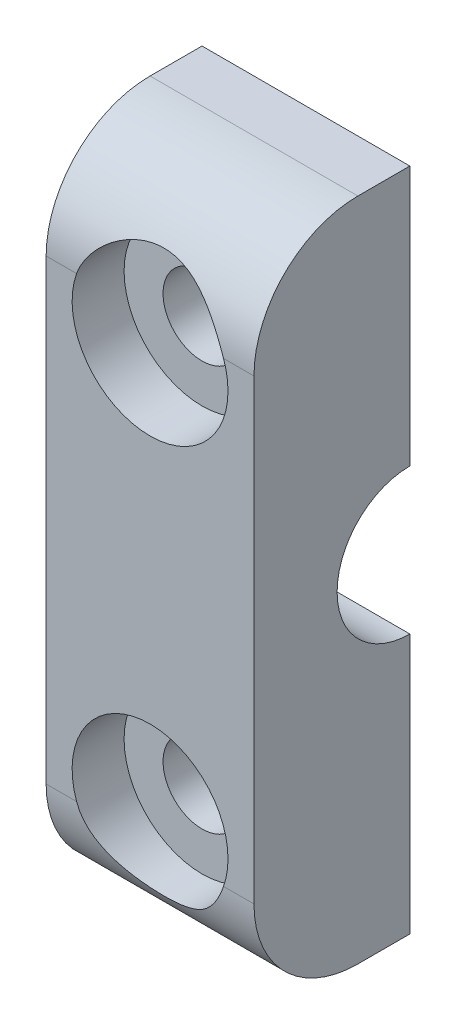
SolidWorks part; units mm, degrees
ref_plane "Alzado" through (0, 0, 0) normal (0, 0, 1) x (1, 0, 0)
ref_plane "Planta" through (0, 0, 0) normal (0, 1, 0) x (1, 0, 0)
ref_plane "Vista lateral" through (0, 0, 0) normal (1, 0, 0) x (0, 0, -1)
sketch "Croquis1" plane through (0, 0, 0) normal (0, 0, 1) x (1, 0, 0)
  line L0 (-132.4409, 66.7992) -> (-124.4409, 66.7992)
  line L1 (-132.4409, 66.7992) -> (-132.4409, 41.1992)
  line L2 (-132.4409, 41.1992) -> (-124.4409, 41.1992)
  line L3 (-124.4409, 66.7992) -> (-124.4409, 41.1992)
  circle A0 centre (-128.4409, 61.7992) radius 1.5
  circle A1 centre (-128.4409, 46.1992) radius 1.5
  dimension "D1" = 25.6
extrude "Saliente-Extruir1" add sketch "Croquis1" along normal blind 6
fillet "Redondeo1" radius 4 2 edges at (-128.4409, 66.7992, 6) (-128.4409, 41.1992, 6)
sketch "Croquis2" plane through (0, 0, 6) normal (0, 0, 1) x (1, 0, 0)
  circle A0 centre (-128.4409, 46.1992) radius 3
  circle A1 centre (-128.4409, 61.7992) radius 3
extrude "Cortar-Extruir1" cut sketch "Croquis2" against normal blind 2
sketch "Croquis3" plane through (-124.4409, 0, 0) normal (1, 0, 0) x (0, 0, -1)
  line L0 (0, 41.1992) -> (0, 66.7992) construction
  circle A0 centre (0, 53.9992) radius 2.8
extrude "Cortar-Extruir2" cut sketch "Croquis3" against normal up to vertex (8 mm away) up to point (-132.4409, 45.1992, 6)
